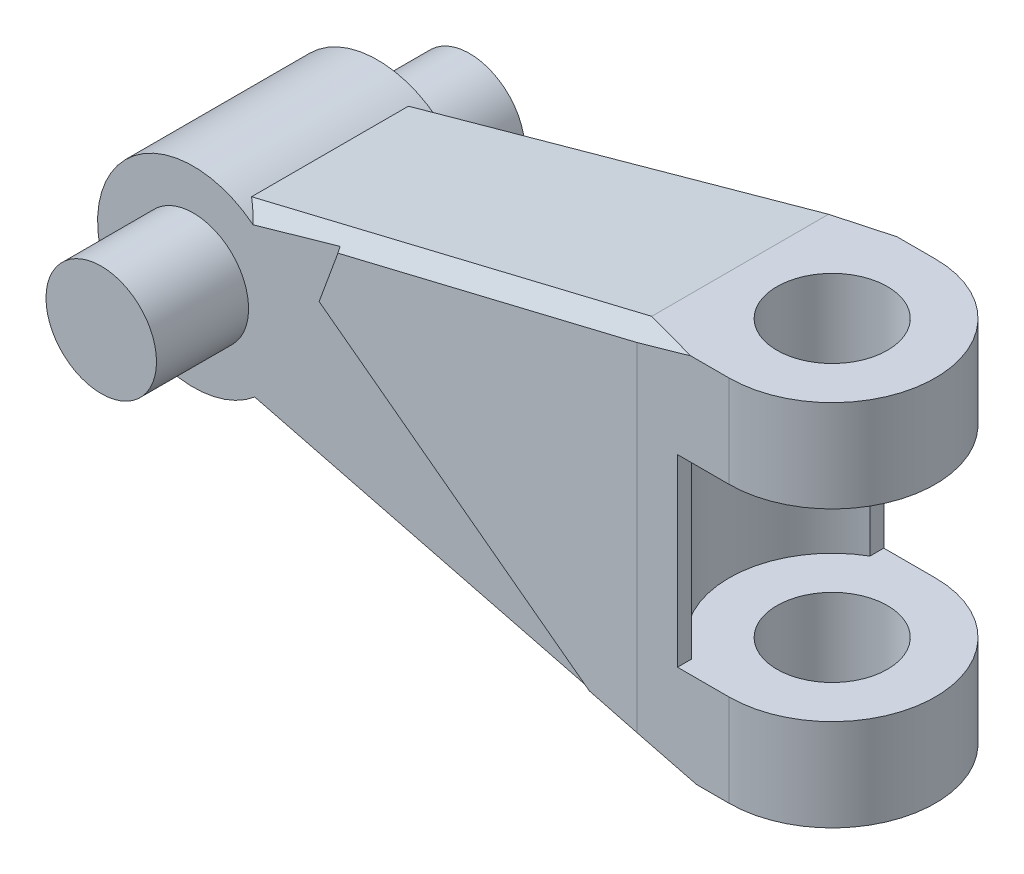
SolidWorks part; units mm, degrees
ref_plane "Alzado" through (0, 0, 0) normal (0, 0, 1) x (1, 0, 0)
ref_plane "Planta" through (0, 0, 0) normal (0, 1, 0) x (1, 0, 0)
ref_plane "Vista lateral" through (0, 0, 0) normal (1, 0, 0) x (0, 0, -1)
sketch "Croquis1" plane through (0, 0, 0) normal (0, 0, 1) x (1, 0, 0)
  line L5 (37.9197, 22.8295) -> (47.7186, 22.8295)
  line L6 (43.4197, 10.3295) -> (43.4197, -14.6705)
  line L7 (47.7186, -27.1705) -> (37.9197, -27.1705)
  line L9 (47.7186, -27.1705) -> (64.9197, -27.1705)
  line L10 (64.9197, -27.1705) -> (64.9197, -14.6705)
  line L11 (64.9197, -14.6705) -> (43.4197, -14.6705)
  line L12 (47.7186, 22.8295) -> (64.9197, 22.8295)
  line L13 (64.9197, 22.8295) -> (64.9197, 10.3295)
  line L14 (64.9197, 10.3295) -> (43.4197, 10.3295)
  line L15 (-23.8038, 6.8045) -> (37.9197, 22.8295)
  line L16 (-23.8038, -13.0383) -> (37.9197, -27.1705)
  arc A0 (-23.8038, 6.8045) -> (-23.8038, -13.0383) centre (-23.8038, -3.1169) ccw
  dimension "D1" = 25
  dimension "D2" = 21.5
  dimension "D3" = 21.5
  dimension "D5" = 50
  dimension "D6" = 12.5
extrude "Saliente-Extruir2" add sketch "Croquis1" along normal blind 28 contours L15 L5 L12 L13 L14 L6 L11 L10 L9 L7 L16 A0
sketch "Croquis5" plane through (0, -27.1705, 0) normal (0, -1, 0) x (1, 0, 0)
  line L0 (50.4197, 28) -> (64.9197, 28)
  line L1 (51.4197, 0) -> (50.4197, 0)
  line L2 (64.9197, 28) -> (64.9197, 0)
  line L3 (64.9197, 0) -> (51.4197, 0)
  line L4 (37.9197, 0) -> (64.9197, 0) construction
  arc A0 (50.4197, 0) -> (50.4197, 28) centre (50.4197, 14) ccw
extrude "Cortar-Extruir1" cut sketch "Croquis5" against normal blind 71
sketch "Croquis8" plane through (0, 0, 28) normal (0, 0, 1) x (1, 0, 0)
  line L2 (67.3293, -2.1705) -> (16.4618, -2.1705) construction
ref_plane "Plano1" through (0, -2.1705, 0) normal (0, -1, 0) x (-1, 0, 0)
sketch "Croquis9" plane through (0, -2.1705, 0) normal (0, -1, 0) x (-1, 0, 0)
  circle A0 centre (-50.4197, -14) radius 14
extrude "Cortar-Extruir4" cut sketch "Croquis9" against normal mid plane 25
sketch "Croquis10" plane through (0, -27.1705, 0) normal (0, -1, 0) x (1, 0, 0)
  circle A0 centre (50.4197, 14) radius 7.5
  dimension "D1" = 15
extrude "Cortar-Extruir5" cut sketch "Croquis10" against normal through all
sketch "Croquis11" plane through (0, 22.8295, 0) normal (0, 1, 0) x (1, 0, 0)
  line L0 (37.9197, 0) -> (-23.8038, -1.5)
  line L1 (-23.8038, -28) -> (-23.8038, 0) construction
  line L3 (-23.8038, -26.5) -> (37.9197, -28)
  line L6 (-23.8038, 0) -> (37.9197, 0)
  line L8 (-23.8038, -28) -> (37.9197, -28)
  line L9 (-23.8038, -26.5) -> (-33.7252, -26.5)
  line L10 (-33.7252, 0) -> (-33.7252, -28) construction
  line L11 (-33.7252, -26.5) -> (-33.7252, -28)
  line L12 (-33.7252, -28) -> (-23.8038, -28) construction
  line L13 (-33.7252, -28) -> (-23.8038, -28)
  line L14 (-23.8038, -1.5) -> (-33.7252, -1.5)
  line L15 (-33.7252, -1.5) -> (-33.7252, 0)
  line L16 (-33.7252, 0) -> (-23.8038, 0)
  dimension "D1" = 25
  dimension "D2" = 1.5
extrude "Cortar-Extruir6" cut sketch "Croquis11" against normal through all
chamfer "Chaflán1" distance 2 angle 45 1 edges at (7.0579, 14.817, 0.75)
chamfer "Chaflán2" distance 2 angle 45 3 edges at (7.0579, -20.1044, 0.75) (7.0579, -20.1044, 27.25) (7.0579, 14.817, 27.25)
sketch "Croquis13" plane through (0, 0, 0) normal (1, 0, 0) x (0, 0, -1)
  line L0 (-14, 6.8045) -> (-14, -13.0383) construction
  line L1 (-24.4994, 6.8045) -> (-3.5006, 6.8045) construction
  line L2 (-24.4885, -13.0383) -> (-3.5115, -13.0383) construction
ref_plane "Plano2" through (0, 0, 14) normal (0, 0, 1) x (1, 0, 0)
sketch "Croquis14" plane through (0, 0, 14) normal (0, 0, 1) x (1, 0, 0)
  line L0 (-23.8038, -10.9866) -> (-23.8038, 4.7255) construction
  circle A0 centre (-23.8038, -3.1305) radius 13
extrude "Saliente-Extruir7" add sketch "Croquis14" along normal mid plane 25
sketch "Croquis16" plane through (0, 0, 28) normal (0, 0, 1) x (1, 0, 0)
  line L0 (-23.8038, -10.9866) -> (-23.8038, 4.7255) construction
  circle A0 centre (-23.8038, -3.1305) radius 14.5
extrude "Cortar-Extruir8" cut sketch "Croquis16" against normal blind 1.5
sketch "Croquis17" plane through (0, 0, 0) normal (0, 0, -1) x (-1, 0, 0)
  line L0 (23.8038, -10.9866) -> (23.8038, 4.7255) construction
  circle A0 centre (23.8038, -3.1305) radius 14.5
extrude "Cortar-Extruir9" cut sketch "Croquis17" against normal blind 1.5
sketch "Croquis18" plane through (0, 0, 1.5) normal (0, 0, -1) x (-1, 0, 0)
  line L6 (6.7054, 2.8174) -> (4.0854, 9.8449)
  line L7 (13.7645, 7.3319) -> (-37.9197, 20.7505) construction
  line L9 (-37.9197, -25.1188) -> (13.5106, -13.3433) construction
  line L13 (4.0854, 9.8449) -> (4.6036, 16.9874)
  line L14 (4.6036, 16.9874) -> (16.7445, 14.3874)
  line L15 (16.7445, 14.3874) -> (14.0185, 7.1237)
  line L16 (14.0185, 7.1237) -> (13.7645, 7.3319)
  line L18 (2.0842, -20.5543) -> (12.2953, -17.957)
  line L19 (12.2953, -17.957) -> (12.9319, -13.4042)
  line L20 (12.9319, -13.4042) -> (13.5106, -13.3433)
  line L22 (-30.9987, -23.5342) -> (-29.4764, -29.794)
  line L23 (-29.4764, -29.794) -> (2.0842, -20.5543)
  line L24 (-30.9987, -23.5342) -> (6.7054, 2.8174)
  arc A0 (13.7645, 7.3319) -> (13.5106, -13.3433) centre (23.8038, -3.1305) ccw
  dimension "D1" = 7.5
  dimension "D2" = 10
  dimension "D3" = 46
  dimension "D4" = 55
  dimension "D5" = 11.9494
extrude "Cortar-Extruir14" cut sketch "Croquis18" along normal blind 25
sketch "Croquis20" plane through (0, 0, 26.5) normal (0, 0, 1) x (1, 0, 0)
  line L0 (-3.6839, 9.9491) -> (-6.3038, 2.9216)
  line L1 (-14.4305, -14.9487) -> (-16.8174, -22.8617)
  line L2 (37.9197, 20.7505) -> (-13.7645, 7.3319) construction
  line L3 (-16.8174, -22.8617) -> (27.474, -36.2218)
  line L8 (-13.7645, 7.3319) -> (-14.9034, 6.8467)
  line L9 (-14.9034, 6.8467) -> (-15.5081, 9.845)
  line L10 (-15.5081, 9.845) -> (-5.7747, 12.1515)
  line L11 (-5.7747, 12.1515) -> (-4.7723, 12.3891)
  line L12 (-4.7723, 12.3891) -> (-3.6839, 9.9491)
  line L13 (-13.5106, -13.3433) -> (-14.0354, -13.2232)
  line L14 (-14.0354, -13.2232) -> (-14.4305, -14.9487)
  line L17 (27.474, -36.2218) -> (31.2816, -23.5989)
  line L18 (-13.5106, -13.3433) -> (37.9197, -25.1188) construction
  line L19 (31.2816, -23.5989) -> (-6.3038, 2.9216)
  arc A2 (-13.5106, -13.3433) -> (-13.7645, 7.3319) centre (-23.8038, -3.1305) ccw
  dimension "D1" = 17.5
  dimension "D3" = 7.5
  dimension "D4" = 55
  dimension "D5" = 46
extrude "Cortar-Extruir16" cut sketch "Croquis20" along normal blind 25
sketch "Croquis21" plane through (0, 0, 14) normal (0, 0, 1) x (1, 0, 0)
  circle A0 centre (-23.8038, -3.1305) radius 7.5
  dimension "D1" = 15
extrude "Saliente-Extruir8" add sketch "Croquis21" along normal mid plane 50
